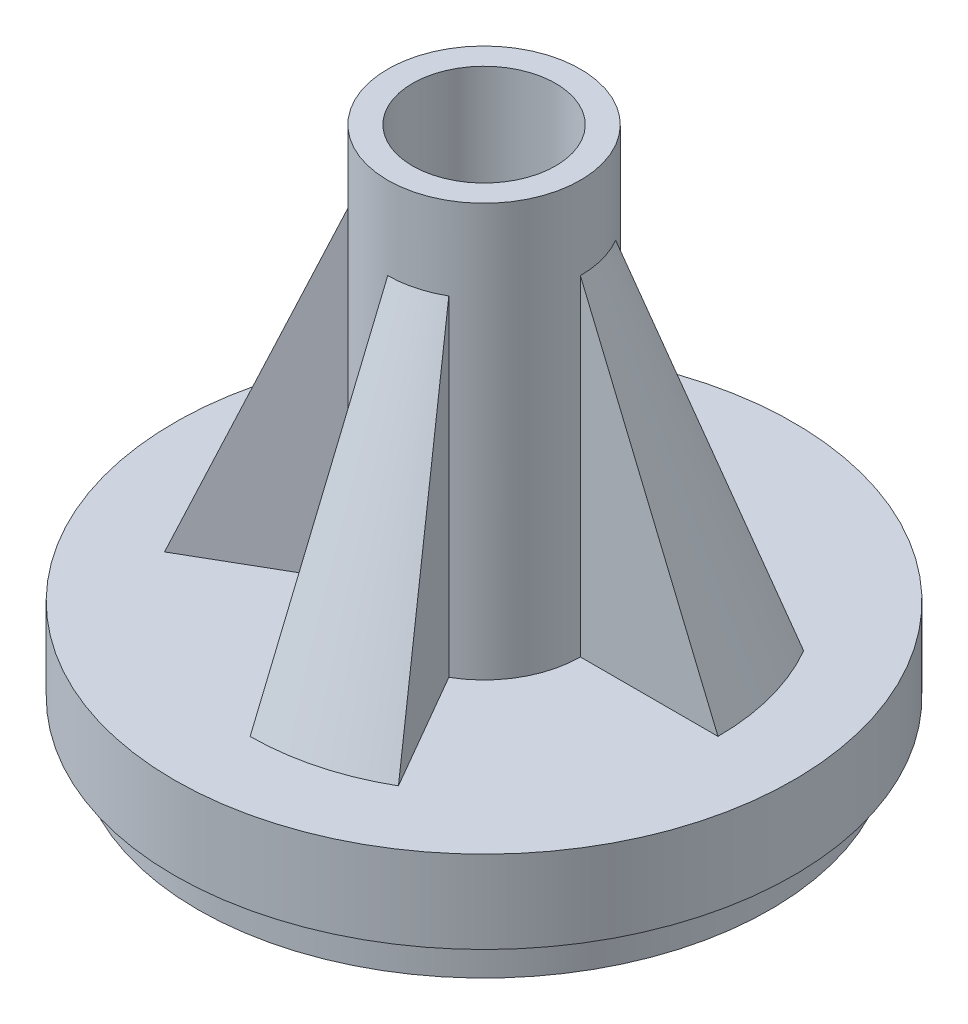
SolidWorks part; units mm, degrees
ref_plane "前视基准面" through (0, 0, 0) normal (0, 0, 1) x (1, 0, 0)
ref_plane "上视基准面" through (0, 0, 0) normal (0, 1, 0) x (1, 0, 0)
ref_plane "右视基准面" through (0, 0, 0) normal (1, 0, 0) x (0, 0, -1)
other "Configuration Table"
sketch "草图1" plane through (0, 0, 0) normal (0, 1, 0) x (1, 0, 0)
  circle A0 centre (0, 0) radius 10.4
  dimension "D1" = 20.8
extrude "凸台-拉伸1" add sketch "草图1" along normal blind 1.5
sketch "草图2" plane through (0, 1.5, 0) normal (0, 1, 0) x (1, 0, 0)
  circle A0 centre (0, 0) radius 11.25
  dimension "D1" = 22.5
extrude "凸台-拉伸2" add sketch "草图2" along normal blind 3
sketch "草图3" plane through (0, 4.5, 0) normal (0, 1, 0) x (1, 0, 0)
  circle A0 centre (0, 0) radius 3.5
  circle A1 centre (0, 0) radius 2.6
  circle A2 centre (0, 0) radius 1.1
  dimension "D1" = 7
  dimension "D2" = 5.2
  dimension "D3" = 2.2
extrude "凸台-拉伸3" add sketch "草图3" along normal blind 15 contours A0 A1 region at (-3.401, 4.5, 0)
extrude "切除-拉伸2" cut sketch "草图3<4>" against normal up to surface (4.5 mm away) contours A2 up to face at (0, 0, 10.4)
sketch "草图3<4>" plane through (0, 4.5, 0) normal (0, 1, 0) x (1, 0, 0) same geometry as "草图3"
sketch "草图6" plane through (0, 0, 0) normal (1, 0, 0) x (0, 0, -1)
  line L0 (0, 0) -> (0, 11.6571) construction
  line L1 (0, 0) -> (14.4338, 0) construction
  line L2 (3.5, 16.5) -> (8.5, 4.5)
  line L3 (3.5, 4.5) -> (3.5, 19.5) construction
  line L4 (11.25, 4.5) -> (-11.25, 4.5) construction
  line L5 (8.5, 4.5) -> (3.5, 4.5)
  line L6 (3.5, 4.5) -> (3.5, 16.5)
  line L7 (-8.5, 4.5) -> (-3.5, 4.5)
  line L8 (-3.5, 16.5) -> (-8.5, 4.5)
  line L9 (-3.5, 4.5) -> (-3.5, 16.5)
  dimension "D1" = 5
  dimension "D2" = 12
revolve "旋转3" add sketch "草图6" angle 30 about L0 region at (0, 8.5, -5.1667) region at (0, 8.5, 5.1667)
sketch "草图9" plane through (0, 0, 0) normal (0, 0, 1) x (1, 0, 0)
  line L0 (3.5, 4.5) -> (8.5, 4.5)
  line L1 (3.5, 16.5) -> (3.5, 4.5)
  line L2 (8.5, 4.5) -> (3.5, 16.5)
  line L3 (3.5, 4.5) -> (3.5, 19.5) construction
  line L4 (0, 0) -> (0, 22.6974) construction
  line L6 (-8.5, 4.5) -> (-3.5, 16.5)
  line L7 (-3.5, 4.5) -> (-8.5, 4.5)
  line L8 (-3.5, 16.5) -> (-3.5, 4.5)
  dimension "D1" = 5
  dimension "D2" = 12
revolve "旋转4" add sketch "草图9" angle 30 about L4
